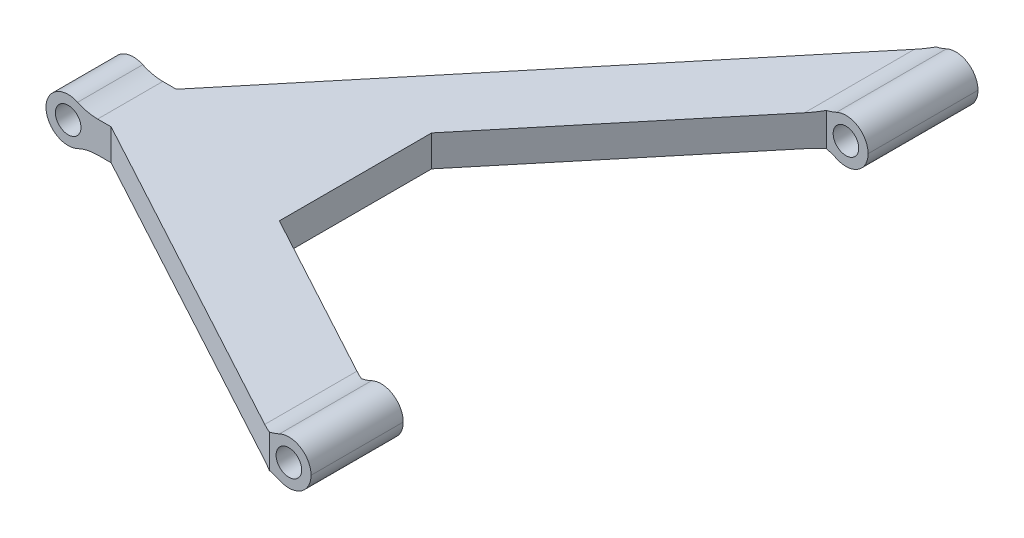
SolidWorks part; units mm, degrees
ref_plane "Front Plane" through (0, 0, 0) normal (0, 0, 1) x (1, 0, 0)
ref_plane "Top Plane" through (0, 0, 0) normal (0, 1, 0) x (1, 0, 0)
ref_plane "Right Plane" through (0, 0, 0) normal (1, 0, 0) x (0, 0, -1)
sketch "Sketch1" plane through (0, 0, 0) normal (0, 1, 0) x (1, 0, 0)
  line L0 (0, -29.761) -> (0, 41.899) construction
  line L1 (0, 41.899) -> (-37, -2.75)
  line L2 (-37, -2.75) -> (-37, -9.75) construction
  line L3 (-37, -9.75) -> (0, -29.761)
  line L4 (-37, -2.75) -> (-44, -2.75)
  line L5 (-44, -2.75) -> (-44, -9.75)
  line L6 (-44, -9.75) -> (-37, -9.75)
  line L7 (0, -29.761) -> (4.4891, -29.761)
  line L8 (4.4891, -29.761) -> (4.4891, -19.8541)
  line L9 (4.4891, -19.8541) -> (0, -19.8541)
  line L10 (0, -19.8541) -> (-19.2165, -9.4611)
  line L11 (-19.2165, -9.4611) -> (-19.2165, 6.9023)
  line L12 (-19.2165, 6.9023) -> (0, 30.0914)
  line L13 (0, 30.0914) -> (4.4891, 30.0914)
  line L14 (4.4891, 30.0914) -> (4.4891, 41.899)
  line L15 (4.4891, 41.899) -> (0, 41.899)
  dimension "D1" = 71.66
  dimension "D2" = 7
  dimension "D3" = 7
  dimension "D4" = 2.75
  dimension "D5" = 44
extrude "Boss-Extrude1" add sketch "Sketch1" along normal blind 2.3813 and the other way blind 2.3813
sketch "Sketch2" plane through (0, 0, 9.75) normal (0, 0, 1) x (1, 0, 0)
  line L0 (-44, 0) -> (-41.6187, 0) construction
  line L1 (4.4891, 0) -> (2.1079, 0) construction
  line L2 (4.4891, 2.3813) -> (4.4891, -2.3813) construction
  line L3 (2.1079, 0) -> (2.1079, 2.3813) construction
  line L4 (0, 2.3813) -> (4.4891, 2.3813) construction
  line L5 (-44, 2.3813) -> (-44, -2.3813) construction
  line L6 (-41.6187, 0) -> (-41.6187, 2.3813) construction
  line L7 (-44, 2.3813) -> (-37, 2.3813) construction
  circle A0 centre (-41.6187, 0) radius 1.375
  circle A1 centre (2.1079, 0) radius 1.375
  dimension "D1" = 2.75
extrude "Cut-Extrude1" cut sketch "Sketch2" against normal through all and the other way through all
fillet "Fillet2" radius 2.3813 6 edges at (4.4891, 2.3813, -35.9952) (4.4891, -2.3813, -35.9952) (4.4891, -2.3813, 24.8075) (4.4891, 2.3813, 24.8075) (-44, -2.3813, 6.25) (-44, 2.3813, 6.25)
sketch "Sketch3" plane through (0, 0, 0) normal (0, 0, 1) x (1, 0, 0)
  line L0 (-38.4509, -1.6736) -> (-1.06, -1.6736)
  line L1 (-41.6188, 0) -> (2.1079, 0) construction
  line L2 (-41.6188, -2.3813) -> (-41.6188, -4.8331)
  line L3 (-41.6188, -4.8331) -> (2.1079, -4.8331)
  line L4 (2.1079, -4.8331) -> (2.1079, -2.3813)
  line L5 (2.1079, 4.8331) -> (2.1079, 2.3812)
  line L6 (-41.6188, 4.8331) -> (2.1079, 4.8331)
  line L7 (-41.6188, 2.3813) -> (-41.6188, 4.8331)
  line L8 (-38.4509, 1.6736) -> (-1.06, 1.6736)
  arc A0 (2.1079, -2.3813) -> (1.0945, -2.1549) centre (2.1079, 0) cw
  arc A1 (-41.6188, -2.3813) -> (-40.6054, -2.1549) centre (-41.6188, 0) ccw
  arc A2 (-40.6054, -2.1549) -> (-38.4509, -1.6736) centre (-38.4509, -6.7364) cw
  arc A3 (1.0945, -2.1549) -> (-1.06, -1.6736) centre (-1.06, -6.7364) ccw
  arc A4 (1.0945, 2.1549) -> (-1.06, 1.6736) centre (-1.06, 6.7364) cw
  arc A5 (-40.6054, 2.1549) -> (-38.4509, 1.6736) centre (-38.4509, 6.7364) ccw
  arc A6 (-41.6188, 2.3813) -> (-40.6054, 2.1549) centre (-41.6188, 0) cw
  arc A7 (2.1079, 2.3812) -> (1.0945, 2.1549) centre (2.1079, 0) ccw
extrude "Cut-Extrude2" cut sketch "Sketch3" against normal through all and the other way through all
